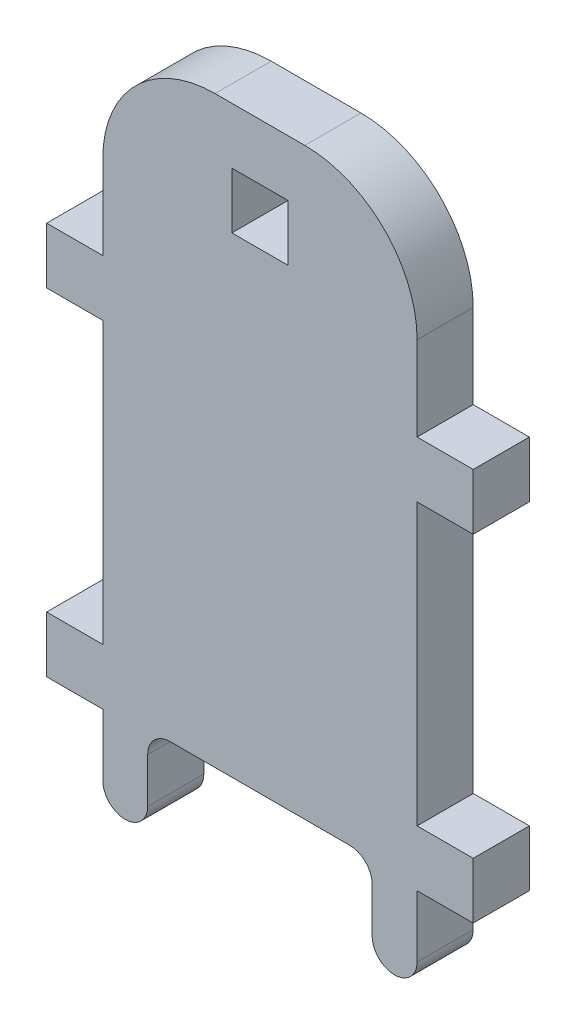
SolidWorks part; units mm, degrees
ref_plane "Plan de face" through (0, 0, 0) normal (0, 0, 1) x (1, 0, 0)
ref_plane "Plan de dessus" through (0, 0, 0) normal (0, 1, 0) x (1, 0, 0)
ref_plane "Plan de droite" through (0, 0, 0) normal (1, 0, 0) x (0, 0, -1)
sketch "Esquisse1" plane through (0, 0, 0) normal (0, 0, 1) x (1, 0, 0)
  line L0 (14, 60) -> (14, 0) construction
  line L1 (0, 0) -> (4, 0)
  line L2 (0, 0) -> (0, 7.5)
  line L3 (0, 60) -> (28, 60)
  line L4 (28, 0) -> (28, 7.5)
  line L5 (0, 42.5) -> (-5, 42.5)
  line L7 (0, 37.5) -> (-5, 37.5)
  line L8 (-5, 42.5) -> (-5, 37.5)
  line L9 (4, 0) -> (4, 8)
  line L10 (28, 37.5) -> (33, 37.5)
  line L11 (33, 42.5) -> (33, 37.5)
  line L12 (28, 42.5) -> (33, 42.5)
  line L13 (28, 7.5) -> (33, 7.5)
  line L14 (33, 7.5) -> (33, 12.5)
  line L15 (28, 12.5) -> (33, 12.5)
  line L16 (0, 12.5) -> (-5, 12.5)
  line L17 (0, 7.5) -> (-5, 7.5)
  line L18 (-5, 7.5) -> (-5, 12.5)
  line L19 (0, 42.5) -> (0, 60)
  line L20 (0, 12.5) -> (0, 37.5)
  line L21 (28, 12.5) -> (28, 37.5)
  line L22 (28, 42.5) -> (28, 60)
  line L23 (4, 8) -> (24, 8)
  line L28 (11.5, 55) -> (16.5, 55)
  line L29 (11.5, 55) -> (11.5, 50)
  line L30 (11.5, 50) -> (16.5, 50)
  line L31 (16.5, 55) -> (16.5, 50)
  line L32 (24, 8) -> (24, 0)
  line L33 (24, 0) -> (28, 0)
  line L34 (4, 0) -> (24, 0) construction
  point P33 (14, 55)
  dimension "D1" = 28
  dimension "D2" = 60
  dimension "D3" = 5
  dimension "D4" = 17.5
  dimension "D5" = 20
  dimension "D6" = 8
  dimension "D9" = 5
  dimension "D10" = 5
  dimension "D11" = 7.5
extrude "Boss.-Extru.1" add sketch "Esquisse1" along normal blind 5
fillet "Congé1" radius 2 2 edges at (24, 8, 2.5) (4, 8, 2.5)
fillet "Congé2" radius 2 4 edges at (24, 0, 2.5) (28, 0, 2.5) (0, 0, 2.5) (4, 0, 2.5)
fillet "Congé3" radius 10 2 edges at (28, 60, 2.5) (0, 60, 2.5)
